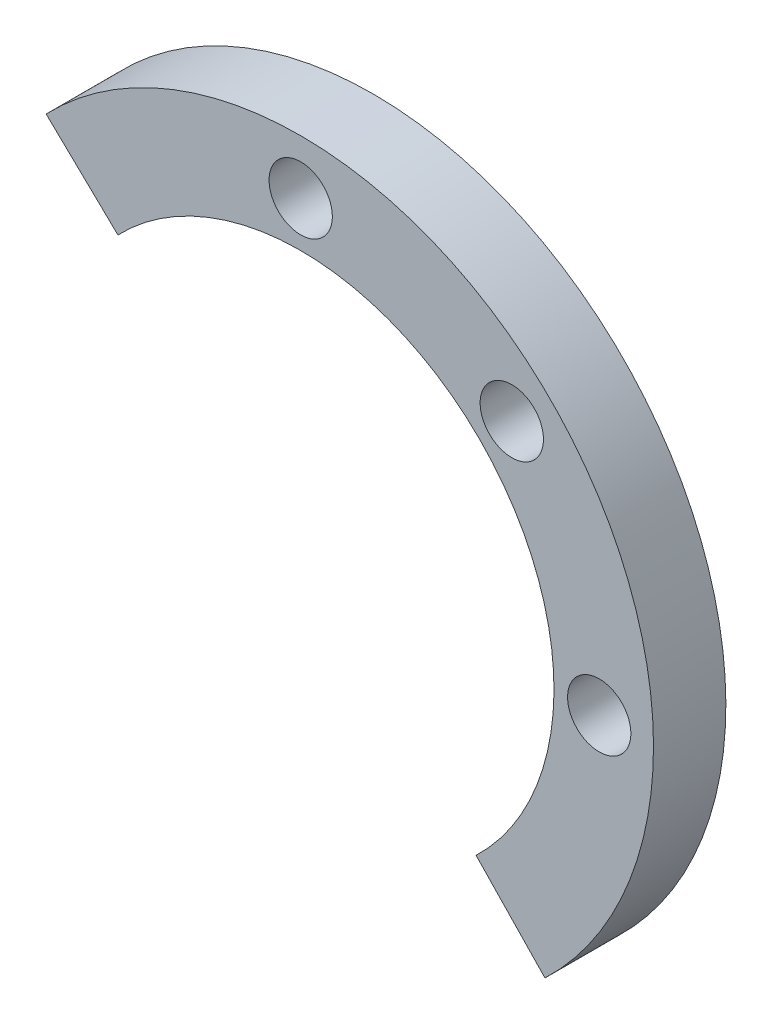
SolidWorks part; units mm, degrees
ref_plane "Front Plane" through (0, 0, 0) normal (0, 0, 1) x (1, 0, 0)
ref_plane "Top Plane" through (0, 0, 0) normal (0, 1, 0) x (1, 0, 0)
ref_plane "Right Plane" through (0, 0, 0) normal (1, 0, 0) x (0, 0, -1)
sketch "Sketch1" plane through (0, 0, 0) normal (0, 0, 1) x (1, 0, 0)
  line L0 (78.5, 50.9288) -> (74.6923, 54.8976)
  line L2 (50.9288, 78.5) -> (54.8976, 74.6923)
  arc A0 (78.5, 50.9288) -> (50.9288, 78.5) centre (65, 65) ccw construction
  arc A1 (78.5, 50.9288) -> (50.9288, 78.5) centre (65, 65) ccw
  circle A2 centre (65, 81.5) radius 1.75 construction
  circle A3 centre (76.6673, 76.6673) radius 1.75 construction
  circle A4 centre (81.5, 65) radius 1.75 construction
  circle A5 centre (65, 81.5) radius 1.75
  circle A6 centre (76.6673, 76.6673) radius 1.75
  circle A7 centre (81.5, 65) radius 1.75
  circle A8 centre (65, 65) radius 14
  circle A9 centre (65, 65) radius 13.5 construction
  dimension "D1" = 0.5
extrude "Boss-Extrude1" add sketch "Sketch1" along normal blind 4 contours A8 L0 A1 L2 A7 A6 A5 region at (76.9387, 53.2418, 0)
